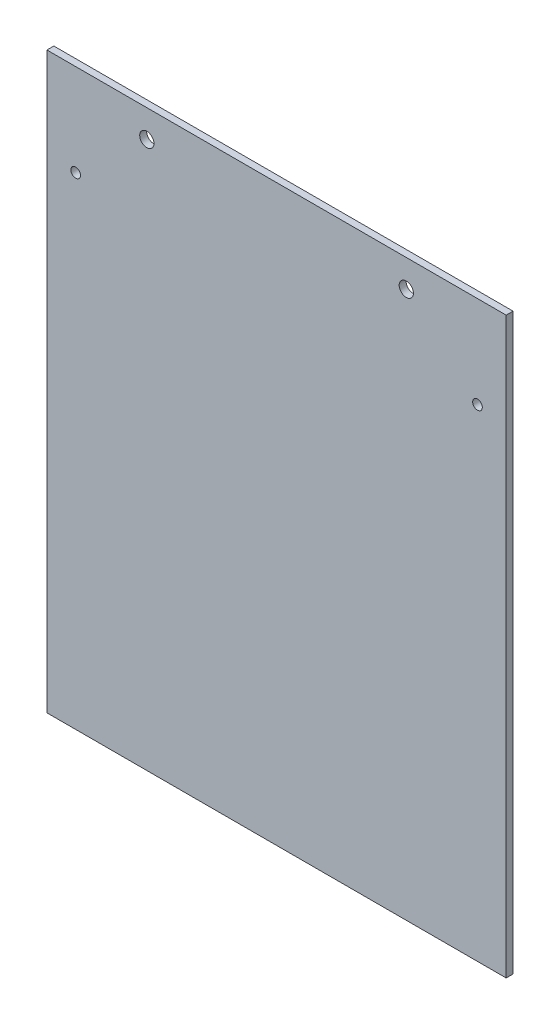
SolidWorks part; units mm, degrees
material "Stop 1060"
ref_plane "Płaszczyzna przednia" through (0, 0, 0) normal (0, 0, 1) x (1, 0, 0)
ref_plane "Płaszczyzna górna" through (0, 0, 0) normal (0, 1, 0) x (1, 0, 0)
ref_plane "Płaszczyzna prawa" through (0, 0, 0) normal (1, 0, 0) x (0, 0, -1)
sketch "Szkic1" plane through (0, 0, 0) normal (0, 0, 1) x (1, 0, 0)
  line L1 (0, 0) -> (200, 0)
  line L2 (0, 0) -> (0, 250)
  line L3 (0, 250) -> (200, 250)
  line L4 (200, 0) -> (200, 250)
  dimension "D1" = 200
  dimension "D2" = 250
extrude "Dodanie-wyciągnięcie1" add sketch "Szkic1" along normal blind 3
sketch "Szkic2" plane through (0, 0, 3) normal (0, 0, 1) x (1, 0, 0)
  line L0 (100, 250) -> (100, 0) construction
  line L1 (200, 250) -> (0, 250) construction
  line L2 (0, 0) -> (200, 0) construction
  line L3 (0, 250) -> (0, 0) construction
  circle A0 centre (12.5, 210) radius 2.1
  circle A1 centre (43.5, 238) radius 3.1
  circle A3 centre (156.5, 238) radius 3.1
  circle A4 centre (187.5, 210) radius 2.1
  dimension "D2" = 40
  dimension "D3" = 12
  dimension "D4" = 43.5
  dimension "D5" = 4.2
  dimension "D6" = 6.2
  dimension "D1" = 12.5
extrude "Wytnij-wyciągnięcie1" cut sketch "Szkic2" against normal through all
